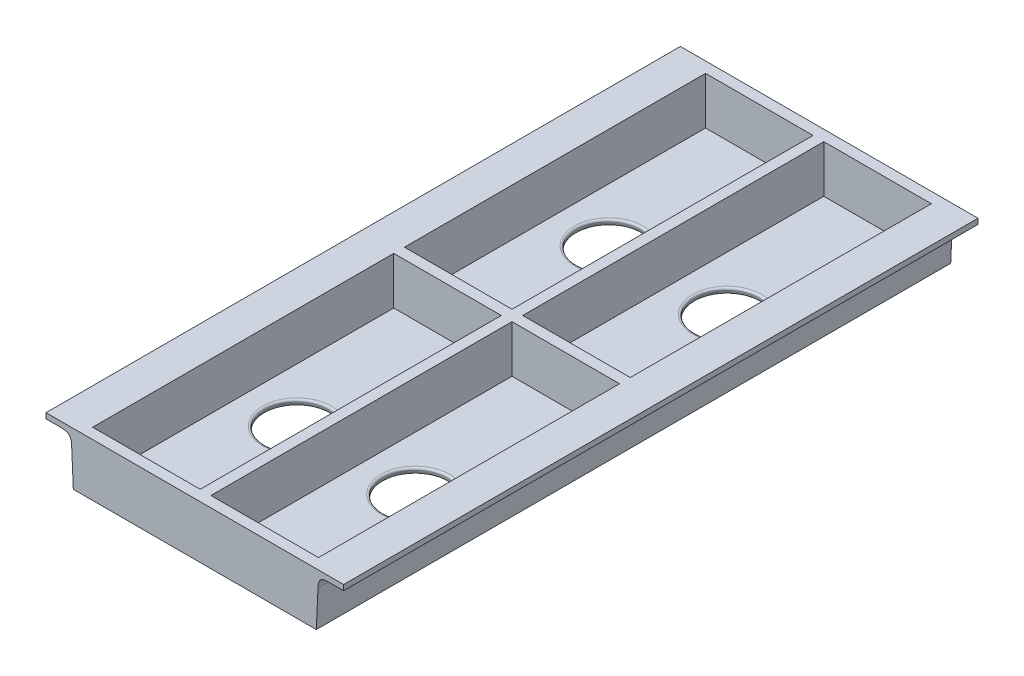
SolidWorks part; units mm, degrees
ref_plane "Front Plane" through (0, 0, 0) normal (0, 0, 1) x (1, 0, 0)
ref_plane "Top Plane" through (0, 0, 0) normal (0, 1, 0) x (1, 0, 0)
ref_plane "Right Plane" through (0, 0, 0) normal (1, 0, 0) x (0, 0, -1)
sketch "Sketch1" plane through (0, 0, 0) normal (0, 0, 1) x (1, 0, 0)
  line L3 (68.7, 0.1099) -> (68.7, -2.3901)
  line L4 (68.7, -2.3901) -> (57, -2.3901)
  line L12 (-69.7, 0.1099) -> (68.7, 0.1099)
  line L13 (-57, -24.3901) -> (56, -24.3901)
  line L14 (56, -24.3901) -> (57, -2.3901)
  line L15 (-57, -24.3901) -> (-58, -2.3901)
  line L16 (-69.7, 0.1099) -> (-69.7, -2.3901)
  line L17 (-69.7, -2.3901) -> (-58, -2.3901)
  dimension "D1" = 2.5
  dimension "D2" = 24.5
  dimension "D3" = 22
  dimension "D4" = 11.7
  dimension "D5" = 138.4
  dimension "D6" = 2.5
  dimension "D7" = 11.7
  dimension "D8" = 22
  dimension "D9" = 24.5
  dimension "D10" = 113
extrude "Boss-Extrude2" add sketch "Sketch1" along normal blind 295 contours L12 L3 L4 L14 L13 L15 L17 L16
sketch "Sketch3" plane through (0, 0.1099, 0) normal (0, 1, 0) x (1, 0, 0)
  line L0 (-0.5, 0) -> (-0.5, -5)
  line L1 (-69.7, 0) -> (68.7, 0) construction
  line L2 (-53, -5) -> (-53, -145)
  line L3 (-53, -5) -> (-3, -5)
  line L4 (2, -5) -> (52, -5)
  line L5 (2, -5) -> (2, -145)
  line L6 (2, -145) -> (52, -145)
  line L7 (52, -5) -> (52, -145)
  line L8 (-3, -5) -> (-3, -145)
  line L9 (-53, -145) -> (-3, -145)
  line L10 (-53, -150) -> (-53, -290)
  line L11 (-53, -150) -> (-3, -150)
  line L12 (-3, -150) -> (-3, -290)
  line L13 (-53, -290) -> (-3, -290)
  line L14 (2, -150) -> (2, -290)
  line L15 (2, -150) -> (52, -150)
  line L16 (52, -150) -> (52, -290)
  line L17 (2, -290) -> (52, -290)
  dimension "D1" = 50
  dimension "D2" = 2.5
  dimension "D3" = 140
  dimension "D4" = 2
  dimension "D5" = 2
extrude "Cut-Extrude1" cut sketch "Sketch3" against normal blind 22 contours L2 L9 L8 L3 | L7 L4 L5 L6 | L11 L12 L13 L10 | L15 L16 L17 L14 region at (-28, 0.1099, 75) region at (27, 0.1099, 75)
sketch "Sketch5" plane through (0, -21.8901, 0) normal (0, 1, 0) x (1, 0, 0)
  line L0 (27, -5) -> (27, -75)
  line L1 (2, -5) -> (52, -5) construction
  circle A0 centre (27, -75) radius 15
  circle A1 centre (-28, -75) radius 15
  circle A2 centre (-28, -220) radius 15
  circle A3 centre (27, -220) radius 15
  dimension "D1" = 2
  dimension "D2" = 2
extrude "Cut-Extrude2" cut sketch "Sketch5" against normal blind 22 contours A1 | A0 | A3 | A2 region at (16.6934, -21.8901, 85.3066) region at (-28, -21.8901, 75) region at (-28, -21.8901, 220) region at (27, -21.8901, 220)
fillet "Fillet1" radius 5 2 edges at (-58, -2.3901, 147.5) (57, -2.3901, 147.5) curvature continuous yes
fillet "Fillet3" radius 1 8 edges at (-28, -24.3901, 90) (-28, -24.3901, 235) (27, -24.3901, 235) (27, -24.3901, 90) (-28, -21.8901, 90) (27, -21.8901, 90) (27, -21.8901, 235) (-28, -21.8901, 235) curvature continuous yes
